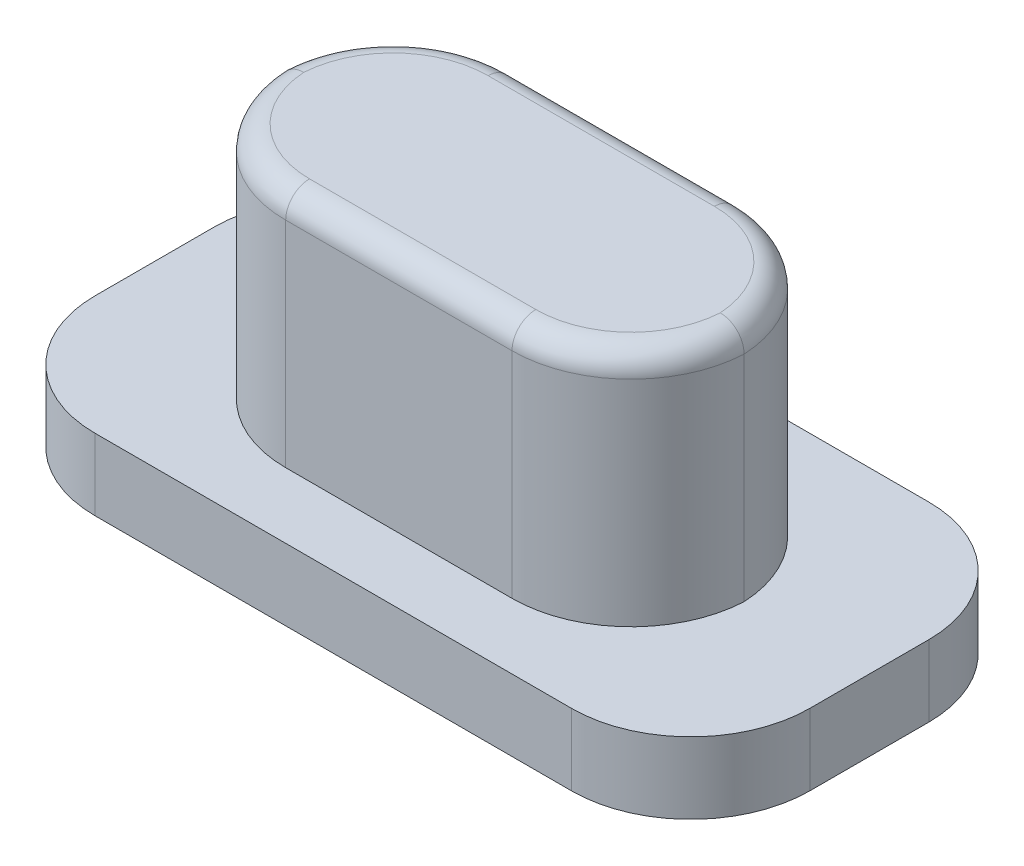
SolidWorks part; units mm, degrees
ref_plane "前视基准面" through (0, 0, 0) normal (0, 0, 1) x (1, 0, 0)
ref_plane "上视基准面" through (0, 0, 0) normal (0, 1, 0) x (1, 0, 0)
ref_plane "右视基准面" through (0, 0, 0) normal (1, 0, 0) x (0, 0, -1)
sketch "草图1" plane through (0, 0, 0) normal (0, 1, 0) x (1, 0, 0)
  line L1 (-2.5031, 1.7604) -> (3.4969, 1.7604)
  line L2 (-2.5031, 1.7604) -> (-2.5031, -1.2396)
  line L3 (-2.5031, -1.2396) -> (3.4969, -1.2396)
  line L4 (3.4969, 1.7604) -> (3.4969, -1.2396)
  dimension "D1" = 6
  dimension "D2" = 3
extrude "凸台-拉伸1" add sketch "草图1" along normal blind 0.6
sketch "草图2" plane through (0, 0.6, 0) normal (0, 1, 0) x (1, 0, 0)
  line L0 (3.4969, 1.7604) -> (-2.5031, 1.7604) construction
  line L1 (-1.4531, 1.2104) -> (2.4469, 1.2104)
  line L2 (-1.4531, 1.2104) -> (-1.4531, -0.6896)
  line L3 (-1.4531, -0.6896) -> (2.4469, -0.6896)
  line L4 (2.4469, 1.2104) -> (2.4469, -0.6896)
  line L5 (-1.4531, 1.2104) -> (2.4469, -0.6896) construction
  line L6 (-1.4531, -0.6896) -> (2.4469, 1.2104) construction
  line L7 (-2.5031, 1.7604) -> (-2.5031, -1.2396) construction
  point P0 (0.4969, 0.2604)
  point P5 (0, 0)
  point P8 (0.4969, 1.7604)
  point P9 (0, 0)
  point P12 (-2.5031, 0.2604)
  dimension "D1" = 3.9
  dimension "D2" = 1.9
extrude "凸台-拉伸2" add sketch "草图2" along normal blind 2
fillet "圆角1" radius 1 8 edges at (3.4969, 0.3, -1.7604) (3.4969, 0.3, 1.2396) (-2.5031, 0.3, -1.7604) (-2.5031, 0.3, 1.2396) (2.4469, 1.6, -1.2104) (-1.4531, 1.6, -1.2104) (-1.4531, 1.6, 0.6896) (2.4469, 1.6, 0.6896)
sketch "草图3" plane through (0, 0, 0) normal (0, -1, 0) x (-1, 0, 0)
  line L0 (1.5031, -1.2396) -> (-2.4969, -1.2396) construction
  line L1 (-1.9969, 1.0604) -> (1.0031, 1.0604)
  line L2 (-1.9969, 1.0604) -> (-1.9969, -0.5396)
  line L3 (-1.9969, -0.5396) -> (1.0031, -0.5396)
  line L4 (1.0031, 1.0604) -> (1.0031, -0.5396)
  line L5 (-1.9969, 1.0604) -> (1.0031, -0.5396) construction
  line L6 (-1.9969, -0.5396) -> (1.0031, 1.0604) construction
  line L7 (2.5031, 0.7604) -> (2.5031, -0.2396) construction
  point P0 (-0.4969, 0.2604)
  point P7 (-0.4969, -1.2396)
  point P8 (0, 0)
  point P11 (2.5031, 0.2604)
  dimension "D1" = 3
  dimension "D2" = 1.6
extrude "凸台-拉伸3" add sketch "草图3" along normal blind 0.2
fillet "圆角2" radius 0.2 6 edges at (2.1361, 2.6, -0.9349) (2.1361, 2.6, 0.4142) (0.4969, 2.6, 0.6896) (-1.1423, 2.6, 0.4142) (-1.1423, 2.6, -0.9349) (0.4969, 2.6, -1.2104)
